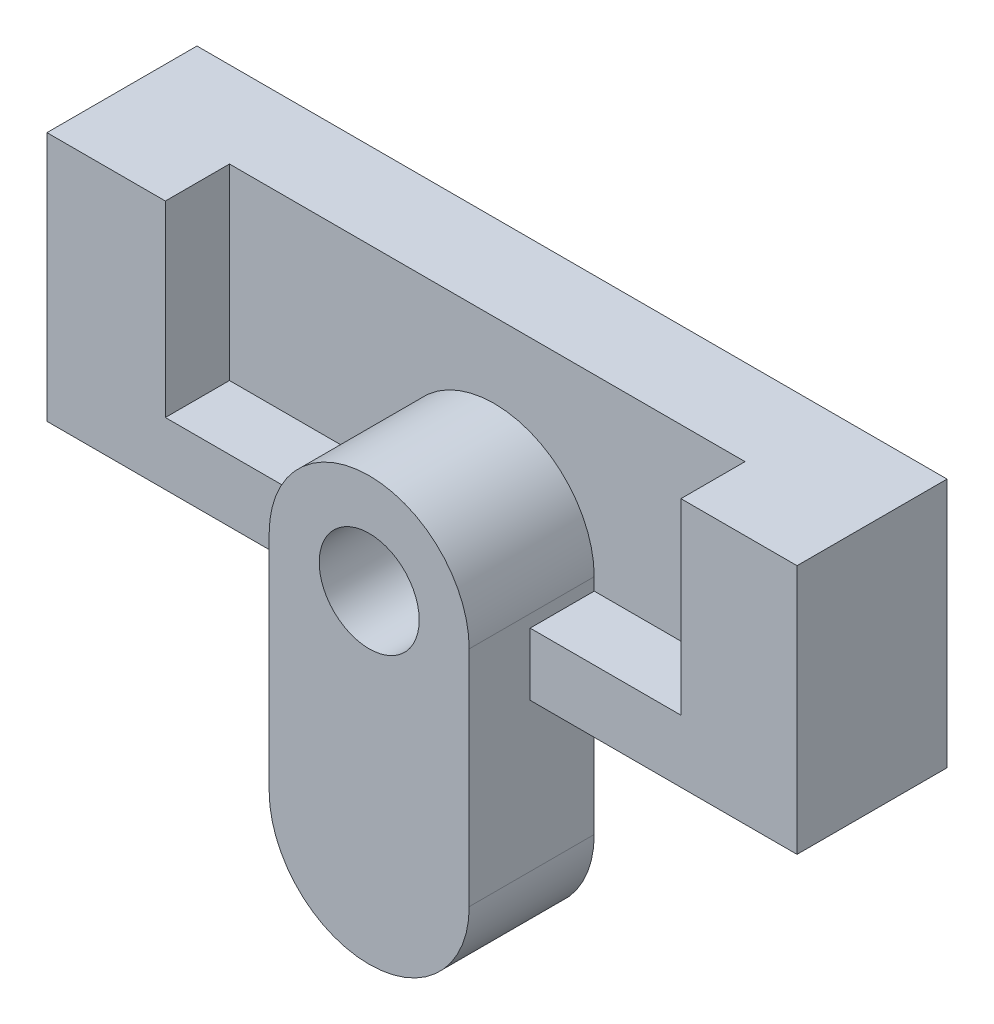
SolidWorks part; units mm, degrees
note: The reader was unsure of these and kept them because the rebuilt part matched: shared geometry of "Sketch3<3>".
material "Cast Alloy Steel"
ref_plane "Front Plane" through (0, 0, 0) normal (0, 0, 1) x (1, 0, 0)
ref_plane "Top Plane" through (0, 0, 0) normal (0, 1, 0) x (1, 0, 0)
ref_plane "Right Plane" through (0, 0, 0) normal (1, 0, 0) x (0, 0, -1)
sketch "Sketch1" plane through (0, 0, 0) normal (0, 1, 0) x (1, 0, 0)
  line L0 (20.0619, 0.7245) -> (29.3498, 0.7245)
  line L1 (-30.6502, 12.7245) -> (29.3498, 12.7245)
  line L2 (-30.6502, 12.7245) -> (-30.6502, 0.7245)
  line L3 (-30.6502, 0.7245) -> (-21.1765, 0.7245)
  line L4 (29.3498, 12.7245) -> (29.3498, 0.7245)
  line L6 (-21.1765, 0.7245) -> (-21.1765, 5.8514)
  line L7 (-21.1765, 5.8514) -> (20.0619, 5.8514)
  line L8 (20.0619, 0.7245) -> (20.0619, 5.8514)
  dimension "D1" = 60
  dimension "D2" = 12
extrude "Boss-Extrude1" add sketch "Sketch1" along normal blind 20 contours L4 L0 L8 L7 L6 L3 L2 L1
sketch "Sketch2" plane through (0, 0, 0) normal (0, -1, 0) x (1, 0, 0)
  line L1 (-30.6502, -0.7245) -> (29.3498, -0.7245)
  line L2 (-30.6502, -0.7245) -> (-30.6502, -12.7245)
  line L3 (-30.6502, -12.7245) -> (29.3498, -12.7245)
  line L4 (29.3498, -0.7245) -> (29.3498, -12.7245)
extrude "Boss-Extrude2" add sketch "Sketch2" against normal blind 5 contours L1 L4 L3 L2
sketch "Sketch3" plane through (0, 0, -5.8514) normal (0, 0, 1) x (1, 0, 0)
  line L0 (0, 0) -> (0, 31.7474) construction
  line L1 (-30.6502, 0) -> (29.3498, 0) construction
  line L3 (-8, 6) -> (8, 6)
  line L4 (-8, 6) -> (-8, -11.8586)
  line L6 (8, 6) -> (8, -11.8586)
  circle A0 centre (0, 6) radius 4
  arc A1 (8, 6) -> (-8, 6) centre (0, 6) ccw
  arc A2 (-8, -11.8586) -> (8, -11.8586) centre (0, -11.8586) ccw
  point P14 (0, -11.8586)
  dimension "D1" = 8
  dimension "D3" = 16
  dimension "D2" = 6
extrude "Boss-Extrude3" add sketch "Sketch3" along normal blind 10
extrude "Cut-Extrude1" cut sketch "Sketch3<3>" against normal through all both and the other way through all contours A0
sketch "Sketch3<3>" plane through (0, 0, -5.8514) normal (0, 0, 1) x (1, 0, 0) same geometry as "Sketch3"
